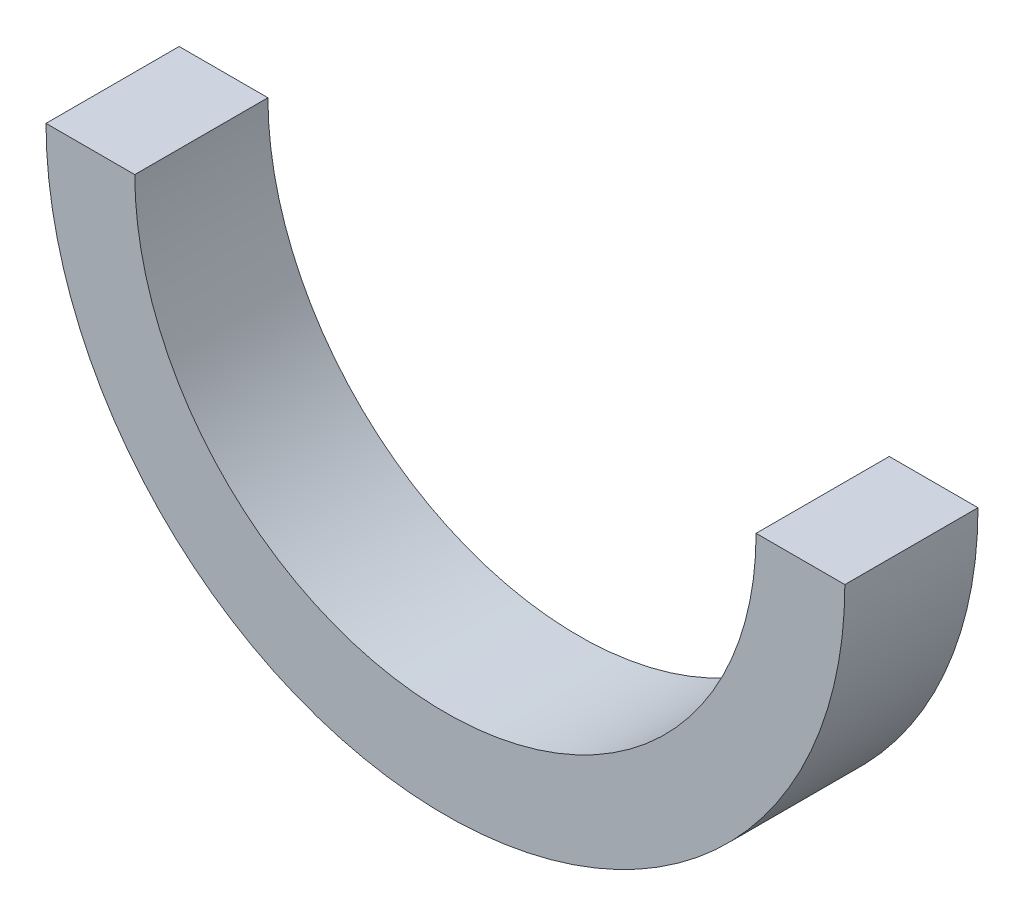
SolidWorks part; units mm, degrees
ref_plane "정면" through (0, 0, 0) normal (0, 0, 1) x (1, 0, 0)
ref_plane "윗면" through (0, 0, 0) normal (0, 1, 0) x (1, 0, 0)
ref_plane "우측면" through (0, 0, 0) normal (1, 0, 0) x (0, 0, -1)
ref_axis "기준축2" through (0, 0, 210) along (0, 0, -1)
ref_axis "기준축4" through (0, 55, 0) along (0, -1, 0)
sketch "스케치1" plane through (0, 0, 0) normal (0, 1, 0) x (1, 0, 0)
  line L0 (40, -7.5) -> (40, 7.5) construction
  line L1 (35, -7.5) -> (45, -7.5)
  line L2 (35, -7.5) -> (35, 7.5)
  line L3 (35, 7.5) -> (45, 7.5)
  line L4 (45, -7.5) -> (45, 7.5)
  point P4 (35, 0)
  dimension "D1" = 15
  dimension "D2" = 10
  dimension "D3" = 40
revolve "회전1" add sketch "스케치1" angle 360 about axis through (0, 0, 210) along (0, 0, -1)
sketch "스케치3" plane through (0, 0, 0) normal (0, 0, 1) x (1, 0, 0)
  line L1 (-78.5289, 68.729) -> (72.7936, 68.729)
  line L2 (-78.5289, 68.729) -> (-78.5289, 0)
  line L3 (-78.5289, 0) -> (72.7936, 0)
  line L4 (72.7936, 68.729) -> (72.7936, 0)
extrude "컷-돌출1" cut sketch "스케치3" against normal mid plane 30
